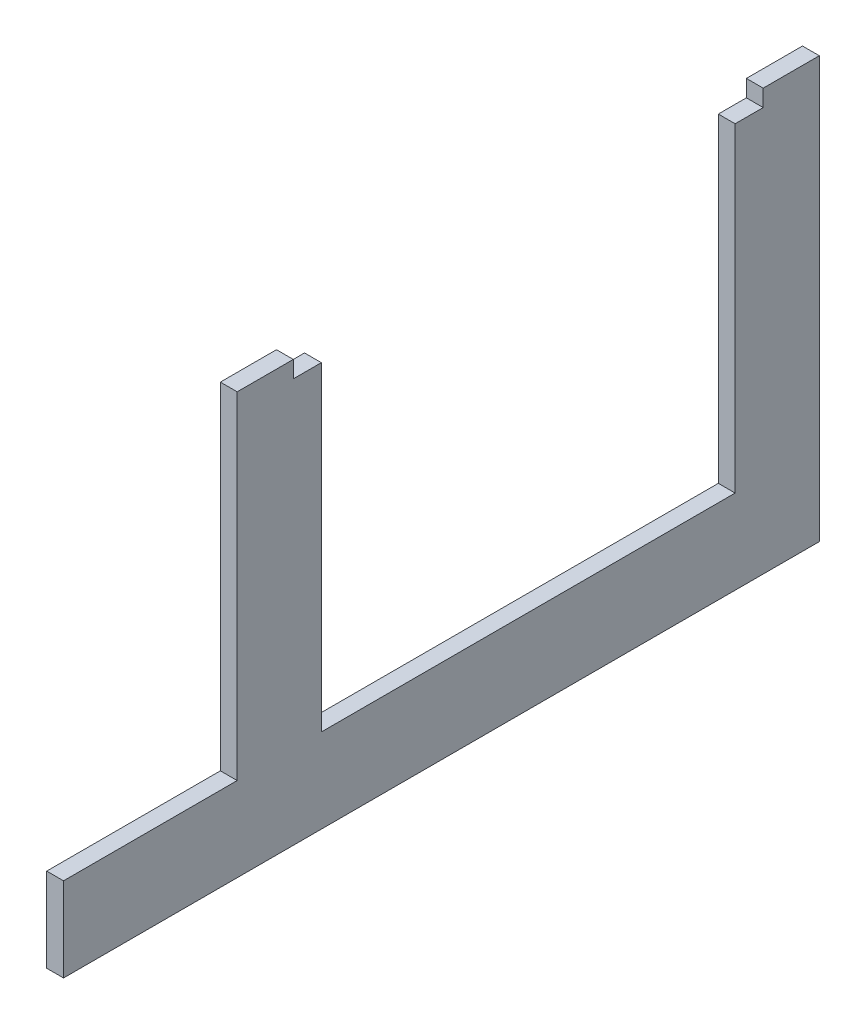
SolidWorks part; units mm, degrees
ref_plane "Front Plane" through (0, 0, 0) normal (0, 0, 1) x (1, 0, 0)
ref_plane "Top Plane" through (0, 0, 0) normal (0, 1, 0) x (1, 0, 0)
ref_plane "Right Plane" through (0, 0, 0) normal (1, 0, 0) x (0, 0, -1)
sketch "Sketch1" plane through (0, 0, 0) normal (0, 1, 0) x (1, 0, 0)
  line L0 (0, 0) -> (0, 103.7444) construction
  line L1 (-36.8722, 0) -> (36.8722, 0) construction
  line L2 (-36.8722, 0) -> (-36.8722, 103.7444)
  line L3 (-36.8722, 103.7444) -> (36.8722, 103.7444)
  line L4 (36.8722, 0) -> (36.8722, 103.7444)
  line L5 (36.8722, 103.7444) -> (36.8722, 0) construction
  line L6 (45.8722, 103.7444) -> (-45.8722, 103.7444) construction
  line L7 (21.0585, 67.686) -> (21.0585, 0)
  line L8 (-21.0585, 67.686) -> (-21.0585, 0)
  line L9 (-36.8722, 0) -> (-21.0585, 0)
  line L10 (21.0585, 0) -> (36.8722, 0)
  line L11 (31.8722, 103.7444) -> (31.8722, 88.7444) construction
  line L12 (34.8722, 103.7444) -> (34.8722, 88.7444) construction
  line L13 (31.8722, 93.7444) -> (34.8722, 93.7444) construction
  line L14 (31.8722, 10) -> (34.8722, 10) construction
  line L15 (31.8722, 88.7444) -> (34.8722, 88.7444) construction
  line L16 (31.8722, 15) -> (34.8722, 15) construction
  line L17 (31.8722, 15) -> (31.8722, 0) construction
  line L18 (34.8722, 15) -> (34.8722, 0) construction
  line L19 (33.3722, 93.7444) -> (33.3722, 88.7444) construction
  line L20 (33.3722, 15) -> (33.3722, 10) construction
  line L21 (34.8722, 100.7444) -> (-34.8722, 100.7444) construction
  line L22 (-34.8722, 100.7444) -> (-34.8722, 103.7444) construction
  line L23 (56.5, -60.95) -> (59.5, -60.95) construction
  arc A0 (21.0585, 67.686) -> (-21.0585, 67.686) centre (0, 67.686) ccw construction
  arc A1 (21.0585, 67.686) -> (-21.0585, 67.686) centre (0, 67.686) ccw
  circle A2 centre (28.9653, 80.8376) radius 1.75 construction
  circle A3 centre (-28.9653, 80.8376) radius 1.75 construction
  circle A4 centre (28.9653, 22.9069) radius 1.75 construction
  circle A5 centre (-28.9653, 22.9069) radius 1.75 construction
  circle A6 centre (28.9653, 80.8376) radius 1.75
  circle A7 centre (-28.9653, 80.8376) radius 1.75
  circle A8 centre (28.9653, 22.9069) radius 1.75
  circle A9 centre (-28.9653, 22.9069) radius 1.75
  dimension "D2" = 2
  dimension "D3" = 10
  dimension "D4" = 5
ref_plane "Plane1" through (34.8722, 0, 0) normal (1, 0, 0) x (0, 0, -1)
sketch "Sketch2" plane through (34.8722, 0, 0) normal (1, 0, 0) x (0, 0, -1)
  line L0 (103.7444, 3) -> (103.7444, -72)
  line L1 (103.7444, -72) -> (-30.95, -72)
  line L2 (0, -57) -> (0, 3)
  line L3 (0, 3) -> (10, 3)
  line L4 (10, 3) -> (10, 0)
  line L5 (10, 0) -> (15, 0)
  line L6 (15, 0) -> (15, -57)
  line L7 (15, -57) -> (88.7444, -57)
  line L8 (88.7444, -57) -> (88.7444, 0)
  line L9 (88.7444, 0) -> (93.7444, 0)
  line L10 (93.7444, 0) -> (93.7444, 3)
  line L11 (93.7444, 3) -> (103.7444, 3)
  line L12 (103.7444, 0) -> (88.7444, 0) construction
  line L13 (93.7444, 0) -> (103.7444, 0) construction
  line L14 (98.7444, 0) -> (98.7444, 3) construction
  line L15 (-30.95, -72) -> (-60.95, -72) construction
  line L16 (15, 0) -> (0, 0) construction
  line L17 (100.7444, 0) -> (103.7444, 0) construction
  line L18 (103.7444, -46) -> (0, -46) construction
  line L19 (-60.95, -72) -> (-60.95, -57) construction
  line L20 (-60.95, -45.3) -> (-60.95, 65.4444) construction
  line L21 (-30.95, -72) -> (-30.95, -57)
  line L22 (-30.95, -57) -> (-60.95, -57) construction
  line L23 (0, -57) -> (-30.95, -57)
  dimension "D1" = 46
  dimension "D2" = 72
  dimension "D3" = 15
  dimension "D4" = 30
extrude "Boss-Extrude1" add sketch "Sketch2" against normal up to vertex (3 mm away) up to point (31.8722, 0, -103.7444)
